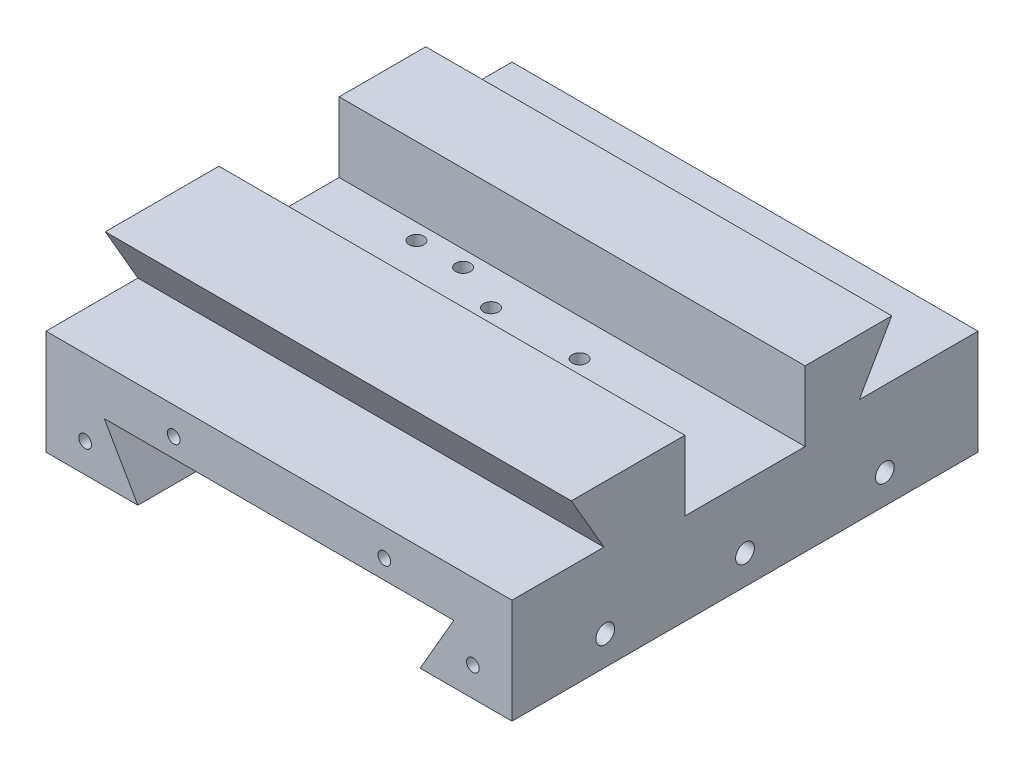
SolidWorks part; units mm, degrees
material "Ductile Iron"
ref_plane "Front Plane" through (0, 0, 0) normal (0, 0, 1) x (1, 0, 0)
ref_plane "Top Plane" through (0, 0, 0) normal (0, 1, 0) x (1, 0, 0)
ref_plane "Right Plane" through (0, 0, 0) normal (1, 0, 0) x (0, 0, -1)
sketch "Sketch10" plane through (0, 0, 0) normal (0, 0, 1) x (1, 0, 0)
  line B0 (-63.5, -15.875) -> (63.5, -15.875)
  line B1 (63.5, 0) -> (38.4596, 0)
  line B2 (38.4596, 0) -> (47.625, 15.875)
  line B3 (47.625, 15.875) -> (16.0563, 15.875)
  line B4 (-40.2927, 15.875) -> (-31.1272, 0)
  line B5 (-31.1272, 0) -> (-63.5, 0)
  line B6 (-63.5, 0) -> (-63.5, -15.875)
  line B7 (-38.4596, 0) -> (-47.625, 15.875)
  line B8 (-47.625, 15.875) -> (-40.2927, 15.875)
  line B9 (-16.0563, 15.875) -> (-16.0563, -3.175) construction
  line B10 (-16.0563, -3.175) -> (16.0563, -3.175) construction
  line B11 (16.0563, -3.175) -> (16.0563, 15.875) construction
  line B12 (-16.0563, 15.875) -> (-40.2927, 15.875)
  line B13 (-63.5, 0) -> (-63.5, 31.75)
  line B14 (-63.5, 31.75) -> (63.5, 31.75)
  line B15 (63.5, 31.75) -> (63.5, 0)
  line B16 (-16.0563, 15.875) -> (16.0563, 15.875) construction
  line B17 (0, 31.75) -> (0, -15.875) construction
  line B18 (-38.4596, 0) -> (38.4596, 0) construction
  line B19 (-28.702, 21.082) -> (28.702, 21.082) construction
  line B20 (-25.4, -8.001) -> (25.4, -8.001) construction
  line B21 (-25.4, -8.001) -> (-25.4, 7.9375) construction
  line B22 (25.4, -8.001) -> (25.4, 7.9375) construction
  line B23 (-52.832, 7.9375) -> (52.832, 7.9375) construction
  circle B24 centre (0, 6.35) radius 18.669 construction
  line B25 (40.2927, 15.875) -> (31.1272, 0)
  line B26 (31.1272, 0) -> (38.4596, 0)
  line B27 (-15.875, 15.875) -> (-15.875, -3.175)
  line B28 (-16.0563, 15.875) -> (-15.875, 15.875)
  line B29 (-15.875, -3.175) -> (15.875, -3.175)
sketch_block_instance "dovetail pair-1"
sketch_block "dovetail pair" parameters "D8"=37.338, "D1"=60, "D2"=127, "D3"=6.35, "D4"=15.875, "D5"=31.75, "D6"=95.25, "D7"=19.05, "D9"=60, "D10"=31.75, "D11"=50.8, "D12"=23.876, "D13"=7.874, "D14"=10.668, "D15"=34.798, "D16"=21.082, "D17"=7.9375, "D18"=24.4437
sketch "Sketch11"
sketch_block_instance "dovetail pair-3"
sketch "female-dovetail-profile" plane through (0, 0, 0) normal (0, 0, 1) x (1, 0, 0)
  line L0 (-47.625, 15.875) -> (-40.2927, 15.875) construction
  line L1 (-16.0563, 15.875) -> (-40.2927, 15.875) construction
  line L2 (-16.0563, 15.875) -> (16.0563, 15.875) construction
  line L3 (47.625, 15.875) -> (16.0563, 15.875) construction
  line L4 (-47.625, 15.875) -> (-40.2927, 15.875)
  line L5 (-16.0563, 15.875) -> (-40.2927, 15.875)
  line L6 (-16.0563, 15.875) -> (16.0563, 15.875)
  line L7 (47.625, 15.875) -> (16.0563, 15.875)
  line L8 (-38.4596, 0) -> (-47.625, 15.875) construction
  line L9 (-63.5, 0) -> (-63.5, 31.75) construction
  line L10 (63.5, 31.75) -> (63.5, 0) construction
  line L11 (63.5, 0) -> (38.4596, 0) construction
  line L12 (38.4596, 0) -> (47.625, 15.875) construction
  line L13 (-38.4596, 0) -> (-47.625, 15.875)
  line L14 (-63.5, 0) -> (-63.5, 31.75)
  line L15 (63.5, 31.75) -> (63.5, 0)
  line L16 (63.5, 0) -> (38.4596, 0)
  line L17 (38.4596, 0) -> (47.625, 15.875)
  line L18 (-38.4596, 0) -> (-63.5, 0)
  line L20 (63.5, 31.75) -> (63.5, 44.45)
  line L21 (63.5, 44.45) -> (-63.5, 44.45)
  line L22 (-63.5, 44.45) -> (-63.5, 31.75)
  dimension "D1" = 44.45
extrude "x-carriage-extrude" add sketch "female-dovetail-profile" along normal mid plane 127
sketch "male-dovetail-shoulder-profile" plane through (0, 0, 0) normal (1, 0, 0) x (0, 0, -1)
  line L0 (40.2927, 44.45) -> (31.1272, 28.575) construction
  line L1 (-40.2927, 44.45) -> (-31.1272, 28.575) construction
  line L2 (38.4596, 28.575) -> (47.625, 44.45) construction
  line L3 (63.5, 28.575) -> (38.4596, 28.575) construction
  line L4 (-38.4596, 28.575) -> (-47.625, 44.45) construction
  line L5 (-40.2927, 44.45) -> (-31.1272, 28.575) construction
  line L6 (38.4596, 28.575) -> (47.625, 44.45) construction
  line L7 (63.5, 28.575) -> (38.4596, 28.575)
  line L8 (-16.0563, 44.45) -> (-16.0563, 25.4) construction
  line L9 (-16.0563, 25.4) -> (16.0563, 25.4) construction
  line L10 (16.0563, 25.4) -> (16.0563, 44.45) construction
  line L11 (47.625, 44.45) -> (16.0563, 44.45) construction
  line L12 (-47.3317, 43.942) -> (-38.4596, 28.575)
  line L14 (-16.0563, 44.45) -> (-16.0563, 25.4) construction
  line L15 (-16.0563, 25.4) -> (16.0563, 25.4) construction
  line L16 (16.0563, 25.4) -> (16.0563, 44.45) construction
  line L17 (47.625, 44.45) -> (16.0563, 44.45) construction
  line L18 (-38.4596, 28.575) -> (-63.5, 28.575)
  line L19 (-16.0563, 44.45) -> (-40.2927, 44.45) construction
  line L20 (-47.3317, 43.942) -> (-16.383, 43.942)
  line L21 (-16.383, 43.942) -> (-16.383, 24.892)
  line L22 (-16.383, 24.892) -> (16.383, 24.892)
  line L23 (16.383, 24.892) -> (16.383, 43.942)
  line L24 (16.383, 43.942) -> (39.9994, 43.942)
  line L25 (39.9994, 43.942) -> (31.1272, 28.575)
  line L26 (-63.5, 28.575) -> (-63.5, 44.45)
  line L27 (-63.5, 44.45) -> (63.5, 44.45)
  line L28 (63.5, 44.45) -> (63.5, 28.575)
  line L29 (0, 60.325) -> (0, 12.7) construction
  line L30 (-31.1272, 28.575) -> (-63.5, 28.575) construction
  line L31 (31.1272, 28.575) -> (38.4596, 28.575)
  line L32 (-15.875, 44.45) -> (-15.875, 25.4) construction
  line L33 (-63.5, 28.575) -> (-63.5, 60.325) construction
  line L34 (-16.0563, 44.45) -> (16.0563, 44.45) construction
  line L35 (-38.4596, 28.575) -> (38.4596, 28.575) construction
  point P16 (0, 24.892)
  dimension "D2" = 0.508
  dimension "D3" = 0.508
  dimension "D1" = 0.508
extrude "y-guide-cut-extrude" cut sketch "male-dovetail-shoulder-profile" against normal mid plane 127
hole_wizard "#8-32 Tapped Hole1" positions "Sketch4" profile "Sketch5" tap size "#8-32" standard "ANSI Inch"
sketch "Sketch4" plane through (0, -15.875, 63.5) normal (0, 0, 1) x (1, 0, 0)
  point P32 (-52.832, 23.8125)
  point P34 (-28.702, 36.957)
  point P36 (28.702, 36.957)
  point P38 (52.832, 23.8125)
cosmetic thread "Hole Thread12" parameters "D1"=8.382, "D2"=4.1656
sketch "Sketch5" plane through (-52.832, 7.9375, 63.5) normal (1, 0, 0) x (0, -1, 0)
  line L0 (0, 0) -> (0, 13.3822)
  line L1 (0, 13.3822) -> (1.7272, 12.3444)
  line L2 (1.7272, 12.3444) -> (1.7272, 0)
  line L3 (1.7272, 0) -> (0, 0)
  line L4 (0, 13.3822) -> (-1.7272, 12.3444) construction
  line L5 (0, -6.35) -> (0, 107.95) construction
  dimension "Tap Drill Dia." = 3.4544
  dimension "Tap Drill Depth" = 12.3444
  dimension "Drill Angle" = 118
cosmetic thread "Hole Thread20" parameters "D1"=8.382, "D2"=4.1656
cosmetic thread "Hole Thread21" parameters "D1"=8.382, "D2"=4.1656
cosmetic thread "Hole Thread22" parameters "D1"=8.382, "D2"=4.1656
hole_wizard "#8-32 Tapped Hole2" positions "Sketch6" profile "Sketch7" tap size "#8-32" standard "ANSI Inch"
sketch "Sketch6" plane through (0, -15.875, -63.5) normal (0, 0, -1) x (-1, 0, 0)
  point P8 (-52.832, 23.8125)
  point P10 (-28.702, 36.957)
  point P12 (28.702, 36.957)
  point P14 (52.832, 23.8125)
cosmetic thread "Hole Thread15" parameters "D1"=8.382, "D2"=4.1656
sketch "Sketch7" plane through (52.832, 7.9375, -63.5) normal (1, 0, 0) x (0, 1, 0)
  line L0 (0, 0) -> (0, 13.4838)
  line L1 (0, 13.4838) -> (1.7272, 12.446)
  line L2 (1.7272, 12.446) -> (1.7272, 0)
  line L5 (1.7272, 0) -> (0, 0)
  line L10 (0, 13.4838) -> (-1.7272, 12.446) construction
  line L11 (0, -6.35) -> (0, 107.95) construction
  dimension "Tap Drill Dia." = 3.4544
  dimension "Tap Drill Depth" = 12.446
  dimension "Drill Angle" = 118
cosmetic thread "Hole Thread23" parameters "D1"=8.382, "D2"=4.1656
cosmetic thread "Hole Thread24" parameters "D1"=8.382, "D2"=4.1656
cosmetic thread "Hole Thread25" parameters "D1"=8.382, "D2"=4.1656
hole_wizard "gib screw 1/4-20 Tapped Hole1" positions "Sketch9" profile "Sketch8" tap size "1/4-20" standard "ANSI Inch" end condition up to next
sketch "Sketch9" plane through (0, 0, 0) normal (1, 0, 0) x (0, 0, -1)
  line L2 (0, 15.875) -> (0, 0) construction
  line L4 (63.5, 7.9375) -> (-63.5, 7.9375) construction
  line L7 (-38.1, 7.9375) -> (0, 7.9375) construction
  line L8 (63.5, 0) -> (63.5, 28.575) construction
  line L9 (-63.5, 15.875) -> (63.5, 15.875) construction
  line L10 (-63.5, 15.875) -> (63.5, 15.875)
  point P0 (-38.1, 7.9375)
  point P16 (0, 7.9375)
  point P22 (0, 7.9375)
  point P23 (38.1, 7.9375)
  dimension "D1" = 38.1
  dimension "D2" = 3
sketch "Sketch8" plane through (0, 7.9375, 38.1) normal (0, 1, 0) x (0, 0, 1)
  line L0 (0, 0) -> (0, 63.5)
  line L1 (0, 63.5) -> (2.5527, 63.5)
  line L2 (2.5527, 63.5) -> (2.5527, 0)
  line L5 (2.5527, 0) -> (0, 0)
  line L11 (0, -6.35) -> (0, 107.95) construction
  dimension "Thru Tap Drill Dia." = 5.1054
  dimension "Thru Tap Drill Depth" = 63.5
cosmetic thread "Hole Thread36" parameters "D1"=23.2203, "D2"=6.35
cosmetic thread "Hole Thread37" parameters "D1"=23.2203, "D2"=6.35
cosmetic thread "Hole Thread38" parameters "D1"=23.2203, "D2"=6.35
hole_wizard "#10-32 Tapped Hole1" positions "Sketch13" profile "Sketch12" tap size "#10-32" standard "ANSI Inch" end condition up to next
sketch "Sketch13" plane through (0, 24.892, 0) normal (0, 1, 0) x (1, 0, 0)
  line L1 (-12.065, -6.35) -> (12.065, -6.35) construction
  line L2 (-12.065, -6.35) -> (-12.065, 6.35) construction
  line L3 (-12.065, 6.35) -> (12.065, 6.35) construction
  line L4 (12.065, -6.35) -> (12.065, 6.35) construction
  line L6 (-38.1, -12.065) -> (-25.4, -12.065) construction
  line L7 (-38.1, -12.065) -> (-38.1, 12.065) construction
  line L8 (-38.1, 12.065) -> (-25.4, 12.065) construction
  line L9 (-25.4, -12.065) -> (-25.4, 12.065) construction
  line L10 (0, 16.383) -> (0, -16.383) construction
  line L12 (-63.5, -16.383) -> (63.5, -16.383) construction
  line L13 (-63.5, 0) -> (63.5, 0) construction
  line L14 (-63.5, -16.383) -> (-63.5, 16.383) construction
  line L15 (63.5, -16.383) -> (63.5, 16.383) construction
  line L16 (-63.5, 16.383) -> (63.5, 16.383) construction
  point P0 (-38.1, 12.065)
  point P2 (-38.1, -12.065)
  point P4 (-12.065, 6.35)
  point P6 (-25.4, 12.065)
  point P8 (-25.4, -12.065)
  point P10 (12.065, 6.35)
  point P12 (12.065, -6.35)
  point P14 (-12.065, -6.35)
  point P155 (0, 0)
  point P157 (0, -6.35)
  point P158 (12.065, 0)
  point P159 (-25.4, 0)
  dimension "D1" = 24.13
  dimension "D2" = 24.13
  dimension "D3" = 12.7
  dimension "D4" = 12.7
  dimension "D5" = 38.1
sketch "Sketch12" plane through (-38.1, 24.892, -12.065) normal (1, 0, 0) x (0, 0, 1)
  line L0 (0, 0) -> (0, 9.017)
  line L1 (0, 9.017) -> (2.0193, 9.017)
  line L2 (2.0193, 9.017) -> (2.0193, 0)
  line L5 (2.0193, 0) -> (0, 0)
  line L11 (0, -6.35) -> (0, 107.95) construction
  dimension "Thru Tap Drill Dia." = 4.0386
  dimension "Thru Tap Drill Depth" = 9.017
cosmetic thread "Hole Thread28" parameters "D2"=4.826
cosmetic thread "Hole Thread29" parameters "D2"=4.826
cosmetic thread "Hole Thread30" parameters "D2"=4.826
cosmetic thread "Hole Thread31" parameters "D2"=4.826
cosmetic thread "Hole Thread32" parameters "D2"=4.826
cosmetic thread "Hole Thread33" parameters "D2"=4.826
cosmetic thread "Hole Thread34" parameters "D2"=4.826
cosmetic thread "Hole Thread35" parameters "D2"=4.826
equation "\"dovetail-angle\" = 60"
equation "\"dovetail-stock-width\" = 5"
equation "\"dovetail-stock-height\" = 1.25"
equation "\"dovetail-depth\" = 0.5 * \"dovetail-stock-height\""
equation "\"dovetail-throat-width\" = \"dovetail-stock-width\" - (2 * \"dovetail-depth\")"
equation "\"delta-x\" = 6"
equation "\"delta-y\" = 3"
equation "\"delta-z\"= 2.5"
equation "\"gib-thickness\" = 0.25"
equation "\"x-slide-length\" = \"dovetail-stock-width\" + \"delta-x\""
equation "\"y-slide-length\" = \"dovetail-stock-width\" + \"delta-y\""
equation "\"dog-point-diam\" = .149"
equation "\"D1@female-dovetail-profile\"=\"dovetail-double-height\""
equation "\"D1@x-carriage-extrude\"=\"dovetail-stock-width\""
equation "\"dog-point-length\" = .067"
equation "\"dovetail-double-height\" = 2 * \"dovetail-depth\" + 0.5"
equation "\"D2@male-dovetail-shoulder-profile\"=\"acme_nut_clearance\""
equation "\"D3@male-dovetail-shoulder-profile\"=\"dovetail_male_clearance\""
equation "\"acme-major-diam\" = .5"
equation "\"acme-pitch-diam\" = 0.45"
equation "\"acme-minor-diam\" = 0.4"
equation "\"acme-nut-od\" = 1.47"
equation "\"acme-nut-length\" = 1"
equation "\"acme-nut-trim-height\" = .75"
equation "\"screw-bearing-od\" = 0.5"
equation "\"screw-bearing-length\" = .375"
equation "\"screw-bearing-id\" = .3125"
equation "\"end-plate-thickness\" = \"screw-bearing-length\""
equation "\"screw-add-length\" = 2 * \"end-plate-thickness\" + 1 + 0.5"
equation "\"x-screw-length\" = \"x-slide-length\" + \"screw-add-length\""
equation "\"y-screw-length\" = \"y-slide-length\" + \"screw-add-length\""
equation "\"acme-nut-mount-hole-space-horz\" = 0.95"
equation "\"acme-nut-mount-hole-space-vert\" = 0.5 * \"acme-nut-length\""
equation "\"D2@dovetail pair\"=\"dovetail-stock-width\""
equation "\"D1@dovetail pair\"=\"dovetail-angle\""
equation "\"D3@dovetail pair\"=\"gib-thickness\""
equation "\"D4@dovetail pair\"=\"dovetail-depth\""
equation "\"D5@dovetail pair\"=\"dovetail-stock-height\""
equation "\"D6@dovetail pair\"=\"dovetail-throat-width\""
equation "\"D10@dovetail pair\"=\"dovetail-stock-height\""
equation "\"D7@dovetail pair\"=\"acme-nut-trim-height\""
equation "\"D8@dovetail pair\"=\"acme-nut-od\""
equation "\"D9@dovetail pair\"=\"dovetail-angle\""
equation "\"D17@dovetail pair\"=\"dovetail-depth\"/2"
equation "\"acme-nut-trim-width\" = 1.25"
equation "\"vise-hole-center-dist\" = 6.75"
equation "\"wiper_plate_clearance\" = .03"
equation "\"dial-width\" = 0.5"
equation "\"quarter-twenty-free-fit\" = .2667"
equation "\"acme_nut_clearance\" = .02"
equation "\"dovetail_male_clearance\" = .02"
equation "\"D1@y-guide-cut-extrude\"=\"dovetail-stock-width\""
equation "\"D1@male-dovetail-shoulder-profile\"=\"acme_nut_clearance\""
equation "\"D1@Sketch13\"=\"acme-nut-mount-hole-space-horz\""
equation "\"D2@Sketch13\"=\"acme-nut-mount-hole-space-horz\""
equation "\"D3@Sketch13\"=\"acme-nut-mount-hole-space-vert\""
equation "\"D4@Sketch13\"=\"acme-nut-mount-hole-space-vert\""
